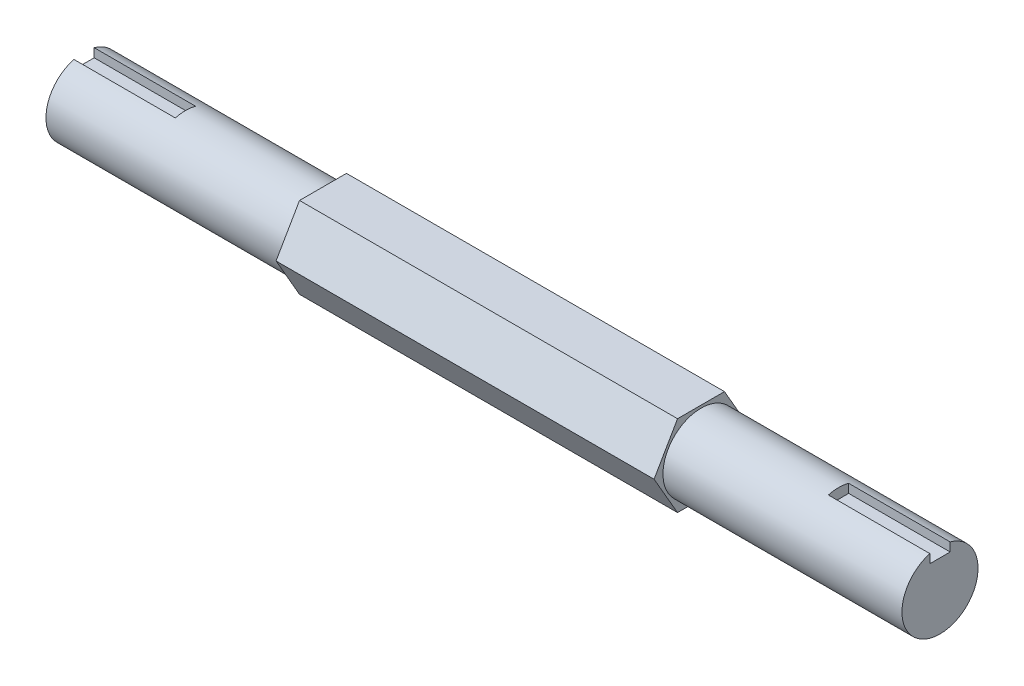
SolidWorks part; units mm, degrees
ref_plane "Front Plane" through (0, 0, 0) normal (0, 0, 1) x (1, 0, 0)
ref_plane "Top Plane" through (0, 0, 0) normal (0, 1, 0) x (1, 0, 0)
ref_plane "Right Plane" through (0, 0, 0) normal (1, 0, 0) x (0, 0, -1)
sketch "Sketch1" plane through (0, 0, 0) normal (1, 0, 0) x (0, 0, -1)
  circle A0 centre (0, 0) radius 15
  dimension "D1" = 30
extrude "Boss-Extrude2" add sketch "Sketch1" along normal mid plane 337.4
sketch "Sketch2" plane through (0, 0, 0) normal (1, 0, 0) x (0, 0, -1)
  line L1 (-18.5041, 0) -> (-9.252, -16.025)
  line L2 (-9.252, -16.025) -> (9.252, -16.025)
  line L3 (9.252, -16.025) -> (18.5041, 0)
  line L4 (18.5041, 0) -> (9.252, 16.025)
  line L5 (9.252, 16.025) -> (-9.252, 16.025)
  line L6 (-9.252, 16.025) -> (-18.5041, 0)
  circle A0 centre (0, 0) radius 16.025 construction
  dimension "D1" = 32.05
extrude "Boss-Extrude3" add sketch "Sketch2" along normal mid plane 149
sketch "Sketch3" plane through (168.7, 0, 0) normal (1, 0, 0) x (0, 0, -1)
  line L0 (0, 17.6275) -> (0, -17.6275) construction
  line L1 (-4, 11) -> (4, 11)
  line L2 (-4, 11) -> (-4, 15)
  line L3 (-4, 15) -> (4, 15)
  line L4 (4, 11) -> (4, 15)
  line L5 (-4, 11) -> (4, 15) construction
  line L6 (-4, 15) -> (4, 11) construction
  circle A0 centre (0, 0) radius 15 construction
  point P0 (0, 13)
  dimension "D1" = 8
  dimension "D2" = 4
extrude "Cut-Extrude1" cut sketch "Sketch3" against normal blind 40
mirror "Mirror1" about plane through (0, 0, 0) normal (1, 0, 0) of "Cut-Extrude1"
sketch "Sketch5" plane through (0, 0, 0) normal (0, 0, 1) x (1, 0, 0)
  line L0 (0, 0) -> (-265.5879, 0) construction
